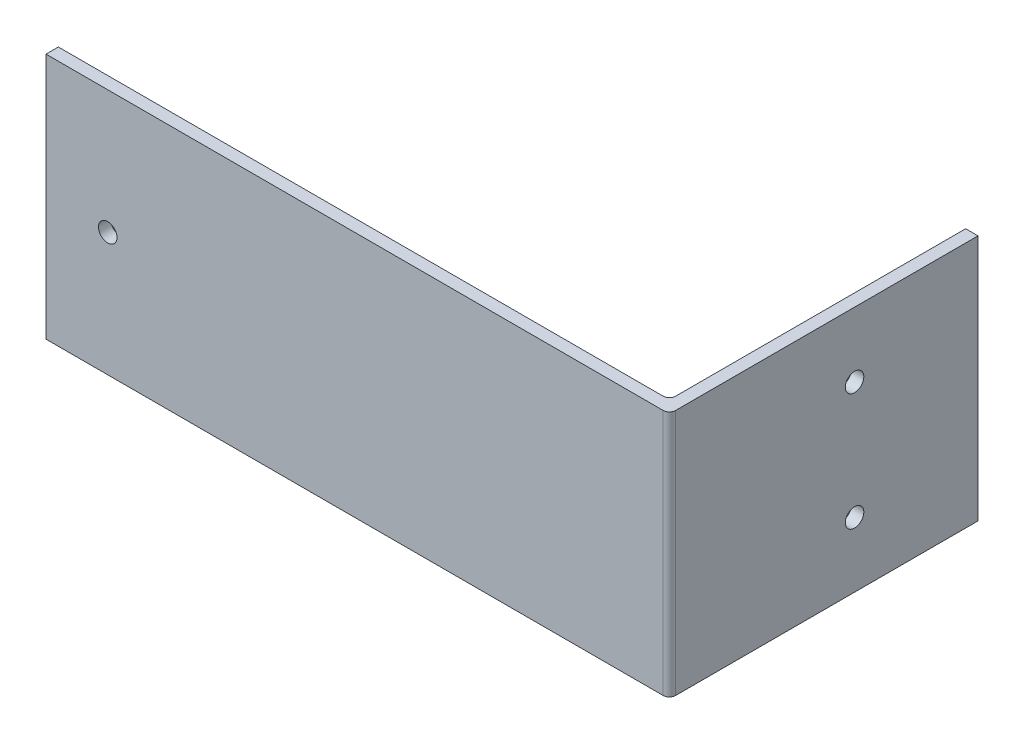
SolidWorks part; units mm, degrees
ref_plane "Front Plane" through (0, 0, 0) normal (0, 0, 1) x (1, 0, 0)
ref_plane "Top Plane" through (0, 0, 0) normal (0, 1, 0) x (1, 0, 0)
ref_plane "Right Plane" through (0, 0, 0) normal (1, 0, 0) x (0, 0, -1)
sketch "Sketch1" plane through (0, 0, 0) normal (0, 0, 1) x (1, 0, 0)
  line L1 (0, 0) -> (100, 0)
  line L2 (0, 0) -> (0, 40)
  line L3 (0, 40) -> (100, 40)
  line L4 (100, 0) -> (100, 40)
  circle A0 centre (10, 20) radius 1.5
  dimension "D3" = 20
  dimension "D4" = 10
  dimension "D1" = 40
  dimension "D2" = 100
extrude "Boss-Extrude1" add sketch "Sketch1" along normal blind 2
sketch "Sketch2" plane through (0, 0, 2) normal (0, 0, 1) x (1, 0, 0)
  line L0 (0, 0) -> (100, 0) construction
  line L1 (100, 40) -> (101, 40)
  line L2 (100, 40) -> (100, 0)
  line L3 (100, 0) -> (101, 0)
  line L4 (101, 40) -> (101, 0)
  line L5 (100, 40) -> (99, 40)
  line L6 (100, 40) -> (100, 0)
  line L7 (100, 0) -> (99, 0)
  line L8 (99, 40) -> (99, 0)
  line M2 (0, 0) -> (100, 0)
  line M3 (100, 0) -> (100, 40)
  line M4 (100, 40) -> (0, 40)
  dimension "D1" = 1
  dimension "D2" = 1
extrude "Boss-Extrude3" add sketch "Sketch2" against normal blind 50 contours L4 L1 L3 M3 | L8 M4 M2 M3 region at (100.5, 20, 2) region at (99.5, 20, 2)
fillet "Fillet2" radius 1 2 edges at (101, 20, 2) (99, 20, 0)
sketch "Sketch3" plane through (101, 0, 0) normal (1, 0, 0) x (0, 0, -1)
  line L0 (48, 20) -> (28, 20)
  line L1 (48, 40) -> (48, 0) construction
  line L2 (28, 20) -> (28, 10.5)
  line L3 (28, 20) -> (28, 29.5)
  circle A0 centre (28, 10.5) radius 1.5
  circle A1 centre (28, 29.5) radius 1.5
  dimension "D1" = 9.5
  dimension "D2" = 9.5
extrude "Cut-Extrude1" cut sketch "Sketch3" against normal blind 10 contours A1 | A0 region at (101, 11.5307, -29.0307) region at (101, 30.5307, -26.9693)
